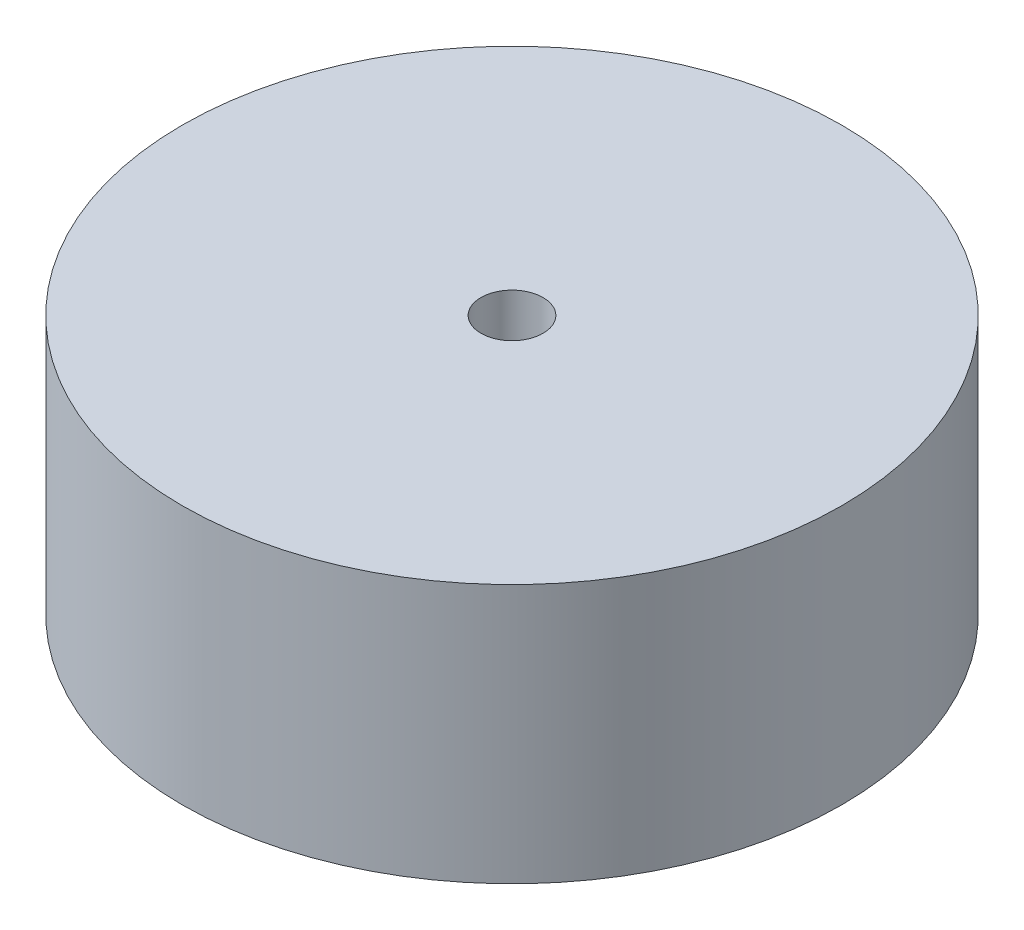
SolidWorks part; units mm, degrees
ref_plane "前基準面" through (0, 0, 0) normal (0, 0, 1) x (1, 0, 0)
ref_plane "上基準面" through (0, 0, 0) normal (0, 1, 0) x (1, 0, 0)
ref_plane "右基準面" through (0, 0, 0) normal (1, 0, 0) x (0, 0, -1)
sketch "草圖1" plane through (0, 0, 0) normal (0, 1, 0) x (1, 0, 0)
  circle A0 centre (0, 0) radius 42.5
  circle A1 centre (0, 0) radius 4
  dimension "D1" = 85
  dimension "D2" = 8
extrude "填料-伸長1" add sketch "草圖1" along normal blind 16.7 and the other way blind 16.7
